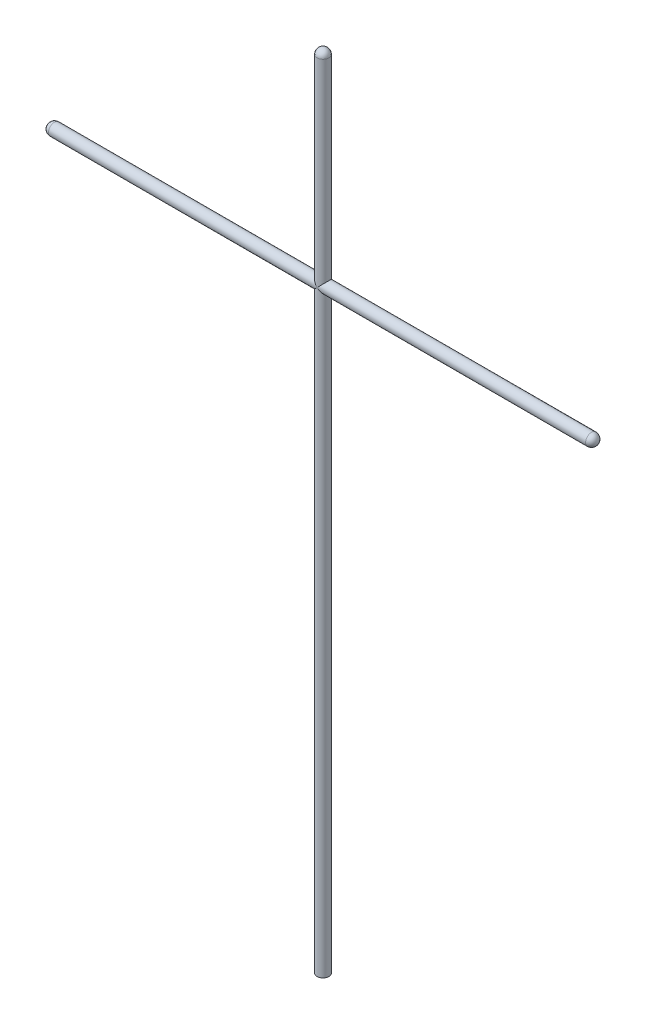
SolidWorks part; units mm, degrees
ref_plane "前视基准面" through (0, 0, 0) normal (0, 0, 1) x (1, 0, 0)
ref_plane "上视基准面" through (0, 0, 0) normal (0, 1, 0) x (1, 0, 0)
ref_plane "右视基准面" through (0, 0, 0) normal (1, 0, 0) x (0, 0, -1)
sketch "草图1" plane through (0, 0, 0) normal (0, 1, 0) x (1, 0, 0)
  circle A0 centre (0, 0) radius 6
  dimension "D1" = 12
extrude "凸台-拉伸1" add sketch "草图1" along normal blind 800
sketch "草图2" plane through (0, 0, 0) normal (1, 0, 0) x (0, 0, -1)
  line L0 (0, -17.5572) -> (0, 882.0579) construction
  circle A0 centre (0, 600) radius 6
  dimension "D1" = 12
  dimension "D2" = 600
extrude "凸台-拉伸2" add sketch "草图2" along normal mid plane 540
sketch "草图3" plane through (270, 0, 0) normal (1, 0, 0) x (0, 0, -1)
  line L0 (0, 606) -> (0, 594)
  circle A1 centre (0, 600) radius 6
  arc A2 (0, 594) -> (0, 606) centre (0, 600) ccw
  dimension "D1" = 0
revolve "旋转1" add sketch "草图3" angle 180 about L0
sketch "草图4" plane through (0, 800, 0) normal (0, 1, 0) x (1, 0, 0)
  line L0 (0, 6) -> (0, -6)
  circle A1 centre (0, 0) radius 6
  arc A2 (0, -6) -> (0, 6) centre (0, 0) ccw
  dimension "D1" = 0
revolve "旋转2" add sketch "草图4" angle 180 about L0
mirror "镜向1" about plane through (0, 0, 0) normal (1, 0, 0) of "旋转1"
ref_axis "基准轴1" through (0, 600, 0) along (-1, 0, 0)
ref_plane "基准面1" through (0, 600, 0) normal (0, 1, 0) x (1, 0, 0)
